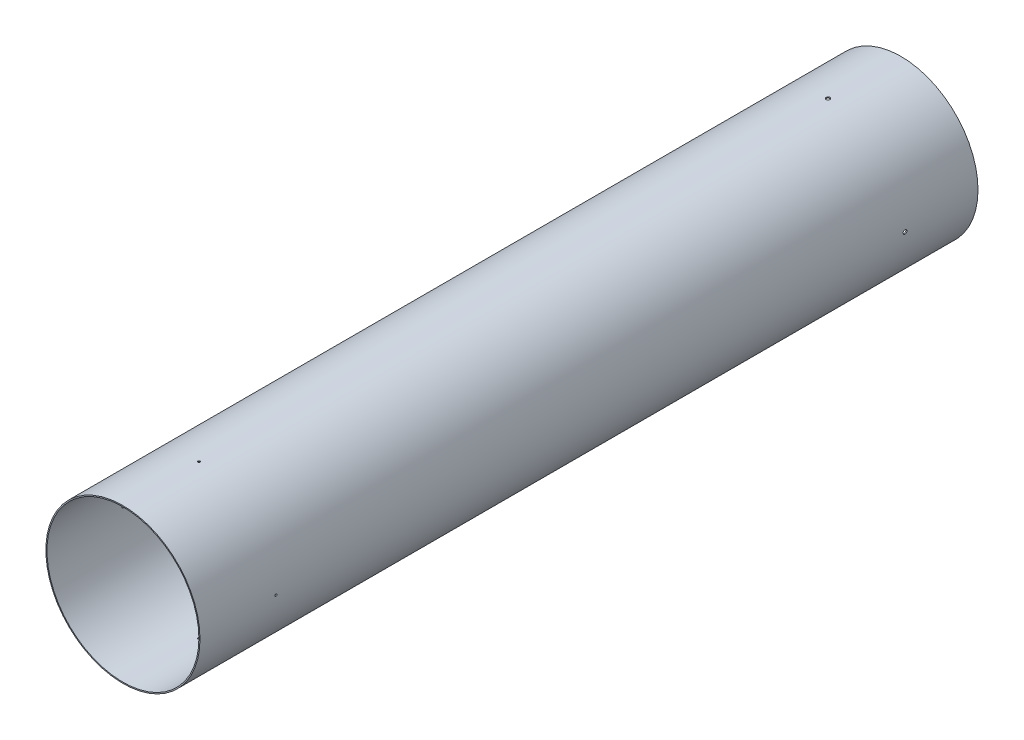
SolidWorks part; units mm, degrees
ref_plane "Front Plane" through (0, 0, 0) normal (0, 0, 1) x (1, 0, 0)
ref_plane "Top Plane" through (0, 0, 0) normal (0, 1, 0) x (1, 0, 0)
ref_plane "Right Plane" through (0, 0, 0) normal (1, 0, 0) x (0, 0, -1)
sketch "Sketch1" plane through (0, 0, 0) normal (0, 0, 1) x (1, 0, 0)
  circle A0 centre (0, 0) radius 79.375
  circle A1 centre (0, 0) radius 80.518
  dimension "D1" = 158.75
  dimension "D2" = 1.143
extrude "Boss-Extrude1" add sketch "Sketch1" along normal blind 812.8
ref_plane "Plane1" through (0, 80.518, 0) normal (0, 1, 0) x (1, 0, 0)
sketch "Sketch2" plane through (0, 80.518, 0) normal (0, 1, 0) x (1, 0, 0)
  line L0 (80.518, 0) -> (-80.518, 0) construction
  point P0 (0, -76.2)
  dimension "D1" = 76.2
hole_wizard "Tap Drill for #10-32 Tap1" positions "Sketch3" profile "Sketch4" hole size "#10-32" standard "ANSI Inch" end condition up to next
sketch "Sketch3" plane through (0, 80.518, 0) normal (0, 1, 0) x (1, 0, 0)
  point P0 (0, -76.2)
sketch "Sketch4" plane through (0, 80.518, 76.2) normal (1, 0, 0) x (0, 0, 1)
  line L0 (0, 0) -> (0, 1.143)
  line L1 (0, 1.143) -> (2.0193, 1.143)
  line L2 (2.0193, 1.143) -> (2.0193, 0)
  line L5 (2.0193, 0) -> (0, 0)
  line L11 (0, -6.35) -> (0, 107.95) construction
  dimension "Thru Hole Dia." = 4.0386
  dimension "Thru Hole Depth" = 1.143
sketch "Sketch5" plane through (0, 80.518, 0) normal (0, 1, 0) x (1, 0, 0)
  line L0 (-80.518, -812.8) -> (80.518, -812.8) construction
  point P0 (0, -733.425)
  dimension "D1" = 79.375
hole_wizard "Tap Drill for #4-40 Tap1" positions "Sketch6" profile "Sketch7" hole size "#4-40" standard "ANSI Inch" end condition up to next
sketch "Sketch6" plane through (0, 80.518, 0) normal (0, 1, 0) x (1, 0, 0)
  point P0 (0, -733.425)
sketch "Sketch7" plane through (0, 80.518, 733.425) normal (1, 0, 0) x (0, 0, 1)
  line L0 (0, 0) -> (0, 1.143)
  line L1 (0, 1.143) -> (1.1303, 1.143)
  line L2 (1.1303, 1.143) -> (1.1303, 0)
  line L5 (1.1303, 0) -> (0, 0)
  line L11 (0, -6.35) -> (0, 107.95) construction
  dimension "Thru Hole Dia." = 2.2606
  dimension "Thru Hole Depth" = 1.143
pattern_circular "CirPattern1" count 4 over 360 about axis through (0, 0, 812.8) along (0, 0, 1) of "Tap Drill for #10-32 Tap1", "Tap Drill for #4-40 Tap1"
